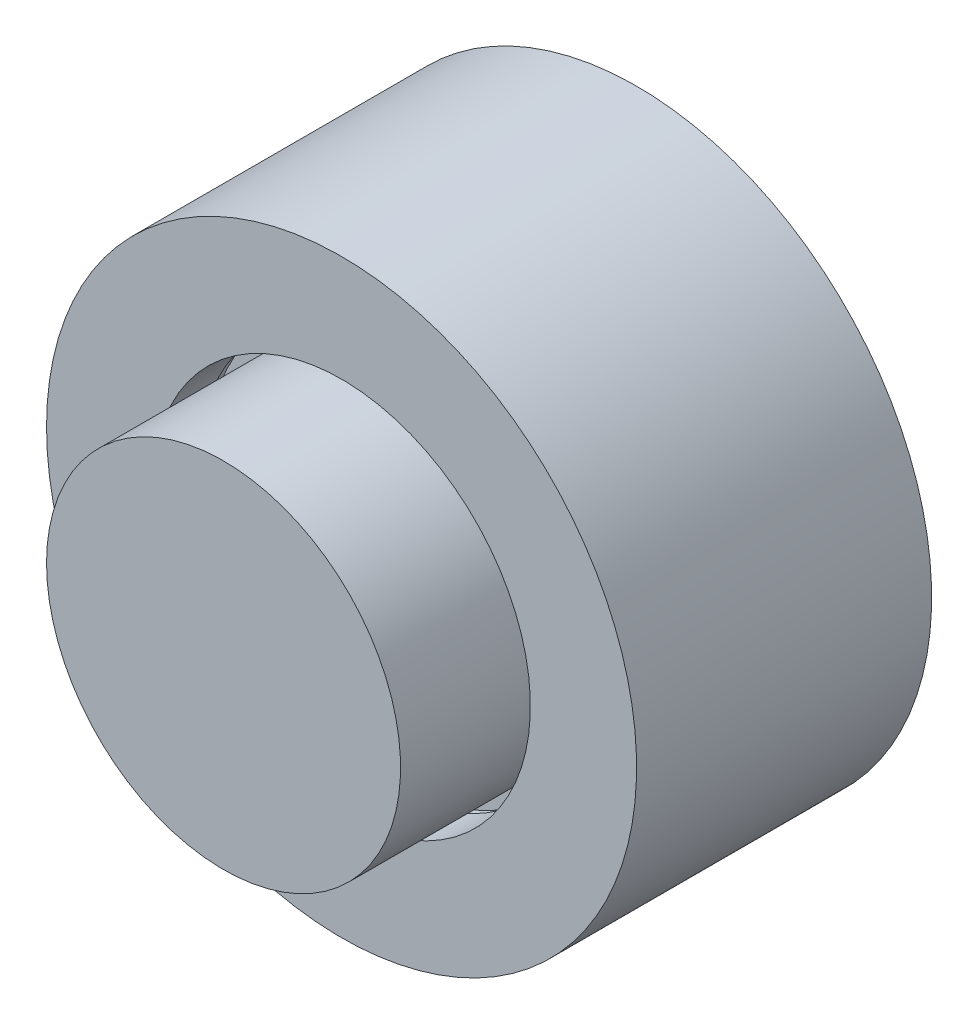
SolidWorks part; units mm, degrees
ref_plane "Front Plane" through (0, 0, 0) normal (0, 0, 1) x (1, 0, 0)
ref_plane "Top Plane" through (0, 0, 0) normal (0, 1, 0) x (1, 0, 0)
ref_plane "Right Plane" through (0, 0, 0) normal (1, 0, 0) x (0, 0, -1)
sketch "Sketch3" plane through (0, 0, 0) normal (0, 1, 0) x (1, 0, 0)
  line L0 (0, 0) -> (3, 0)
  line L1 (3, 0) -> (3, 3)
  line L2 (3, 3) -> (3.25, 3)
  line L3 (3.25, 3) -> (3.25, 4)
  line L4 (3.25, 4) -> (1.5, 4)
  line L5 (1.5, 4) -> (1.5, 1)
  line L6 (1.5, 1) -> (0, 1)
  line L7 (0, 1) -> (0, 0)
  line L8 (0, 0) -> (0, -5.9108) construction
  line L9 (0, 6) -> (3.45, 6)
  line L10 (3.45, 6) -> (3.45, 2.8)
  line L11 (3.45, 2.8) -> (3.2, 2.8)
  line L12 (3.2, 2.8) -> (3.2, 2)
  line L13 (3.2, 2) -> (5, 2)
  line L14 (5, 2) -> (5, 7)
  line L15 (5, 7) -> (0, 7)
  line L16 (0, 7) -> (0, 6)
  dimension "D1" = 3
  dimension "D2" = 0.25
  dimension "D3" = 1.5
  dimension "D4" = 1
  dimension "D5" = 1
  dimension "D6" = 4
  dimension "D7" = 5
  dimension "D8" = 2
  dimension "D9" = 0.2
  dimension "D10" = 0.2
  dimension "D11" = 0.2
  dimension "D12" = 2
  dimension "D13" = 7
revolve "Revolve3" add sketch "Sketch3" angle 360 about L8 region at (1.9879, 0, -1.7581)
revolve "Revolve4" add sketch "Sketch3<3>" angle 360 about L8 region at (3.4526, 0, -5.0684)
sketch "Sketch3<3>" plane through (0, 0, 0) normal (0, 1, 0) x (1, 0, 0) same geometry as "Sketch3"
